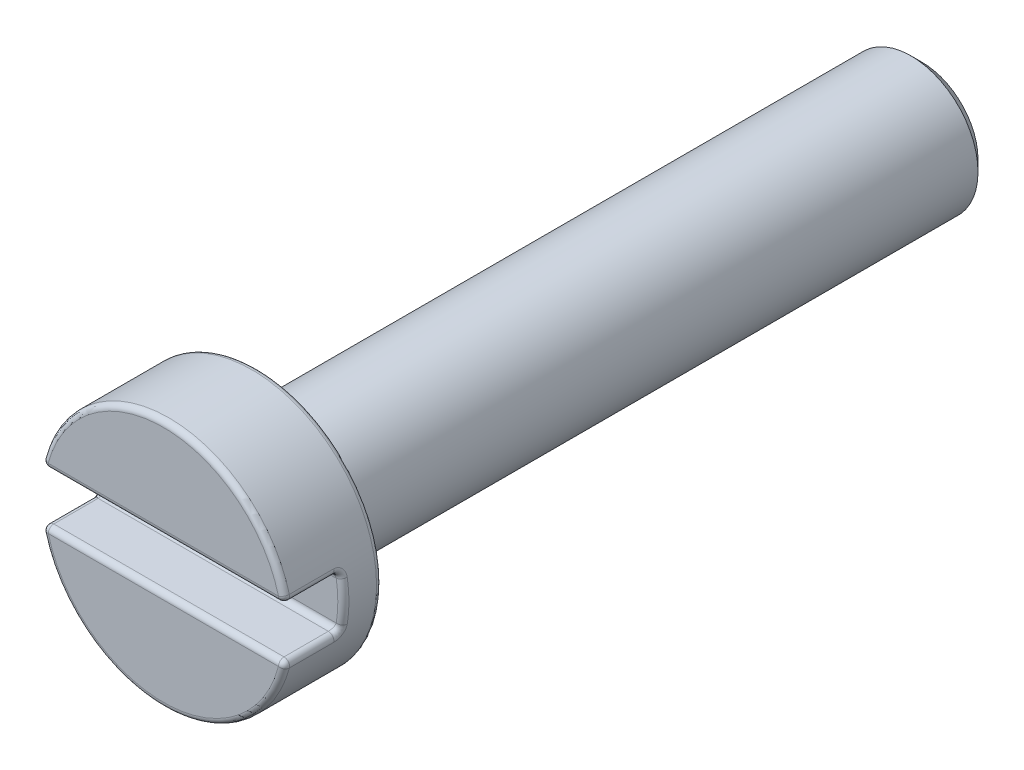
SolidWorks part; units mm, degrees
material "PA Typ 6"
ref_plane "Ebene vorne" through (0, 0, 0) normal (0, 0, 1) x (1, 0, 0)
ref_plane "Ebene oben" through (0, 0, 0) normal (0, 1, 0) x (1, 0, 0)
ref_plane "Ebene rechts" through (0, 0, 0) normal (1, 0, 0) x (0, 0, -1)
sketch "Skizze1" plane through (0, 0, 0) normal (1, 0, 0) x (0, 0, -1)
  line L0 (-21.9199, 0) -> (33.7608, 0) construction
  line L1 (0, 13.9907) -> (0, -9.4798) construction
  line L2 (-1.7, 0) -> (-1.7, 2.25)
  line L3 (-1.7, 2.25) -> (0, 2.25)
  line L4 (0, 2.25) -> (0, 1.21)
  line L5 (0, 1.21) -> (12, 1.21)
  line L6 (12, 1.21) -> (12, 0)
  line L7 (12, 0) -> (-1.7, 0)
  dimension "D1" = 2.42
  dimension "D2" = 1.7
  dimension "D3" = 4.5
  dimension "D4" = 12
revolve "Rotation1" add sketch "Skizze1" angle 360 about L0
sketch "Skizze2" plane through (0, 0, 1.7) normal (0, 0, 1) x (1, 0, 0)
  line L0 (0, 8.6995) -> (0, -7.3778) construction
  line L1 (5.1369, 0) -> (-4.5844, 0) construction
  line L2 (2.25, -0.45) -> (-2.25, -0.45)
  line L3 (2.25, -0.45) -> (2.25, 0.45)
  line L4 (2.25, 0.45) -> (-2.25, 0.45)
  line L5 (-2.25, -0.45) -> (-2.25, 0.45)
  circle A0 centre (0, 0) radius 2.25 construction
  dimension "D1" = 0.9
extrude "Schnitt-Linear austragen1" cut sketch "Skizze2" against normal blind 1
chamfer "Fase1" distance 0.2 angle 45 1 edges at (1.21, 0, -12)
fillet "Verrundung2" radius 0.1 13 edges at (0, 0.45, 1.7) (2.25, 0, 0) (2.2045, -0.45, 1.2) (2.25, 0, 0.7) (2.2045, 0.45, 1.2) (0, 2.25, 1.7) (-2.2045, 0.45, 1.2) (-2.25, 0, 0.7) (-2.2045, -0.45, 1.2) (0, -2.25, 1.7) (0, 0.45, 0.7) (0, -0.45, 0.7) (0, -0.45, 1.7)
ref_axis "Achse1" through (0, 0, -19.6323) along (0, 0, 1)
